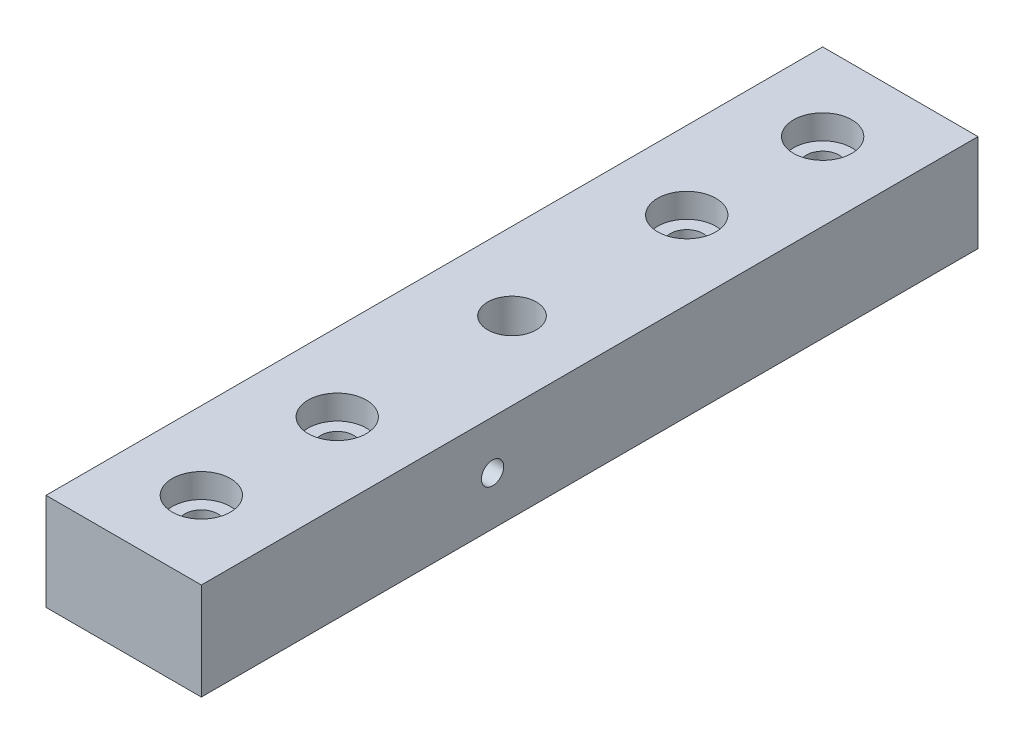
SolidWorks part; units mm, degrees
ref_plane "Ebene vorne" through (0, 0, 0) normal (0, 0, 1) x (1, 0, 0)
ref_plane "Ebene oben" through (0, 0, 0) normal (0, 1, 0) x (1, 0, 0)
ref_plane "Ebene rechts" through (0, 0, 0) normal (1, 0, 0) x (0, 0, -1)
sketch "Sketch1" plane through (0, 0, 0) normal (0, 1, 0) x (1, 0, 0)
  line L0 (0, 88.4363) -> (0, -16.8125) construction
  line L1 (-8, 80) -> (8, 80)
  line L2 (-8, 80) -> (-8, 0)
  line L3 (-8, 0) -> (8, 0)
  line L4 (8, 80) -> (8, 0)
  dimension "D1" = 16
  dimension "D2" = 80
sketch "Sketch2" plane through (0, 0, 0) normal (0, 1, 0) x (1, 0, 0)
  line L0 (0, 87.0713) -> (0, -18.1775) construction
  circle A0 centre (0, 72) radius 2.35
  circle A1 centre (0, 58) radius 2.35
  circle A2 centre (0, 22) radius 2.35
  circle A3 centre (0, 8) radius 2.35
  circle A4 centre (0, 72) radius 3
  circle A5 centre (0, 58) radius 3
  circle A6 centre (0, 22) radius 3
  circle A7 centre (0, 8) radius 3
  circle A8 centre (0, 72) radius 1.7
  circle A9 centre (0, 58) radius 1.7
  circle A10 centre (0, 22) radius 1.7
  circle A11 centre (0, 8) radius 1.7
  dimension "D3" = 4.7
  dimension "D1" = 6
  dimension "D2" = 3.4
  dimension "D4" = 14
  dimension "D5" = 14
  dimension "D6" = 50
  dimension "D7" = 8
extrude "Boss-Extrude1" add sketch "Sketch1" along normal blind 10
extrude "Cut-Extrude1" cut sketch "Sketch2" along normal blind 2.5 contours A0 | A1 | A2 | A3
extrude "Cut-Extrude2" cut sketch "Sketch2<3>" along normal through all contours A8 | A9 | A10 | A11
sketch "Sketch2<3>" plane through (0, 0, 0) normal (0, 1, 0) x (1, 0, 0) same geometry as "Sketch2"
extrude "Cut-Extrude3" cut sketch "Sketch2<4>" along normal through all from offset 7.5 contours A4 | A5 | A6 | A7
sketch "Sketch2<4>" plane through (0, 0, 0) normal (0, 1, 0) x (1, 0, 0) same geometry as "Sketch2"
sketch "Sketch3" plane through (8, 0, 0) normal (1, 0, 0) x (0, 0, -1)
  circle A0 centre (30, 5) radius 1.15
  dimension "D1" = 2.3
  dimension "D2" = 5
  dimension "D3" = 30
extrude "Cut-Extrude4" cut sketch "Sketch3" against normal through all
sketch "Sketch4" plane through (0, 10, 0) normal (0, -1, 0) x (1, 0, 0)
  line L0 (0, 0) -> (0, -80) construction
  line L1 (8, -80) -> (-8, -80) construction
  line L3 (2.2916, -44.0102) -> (4.6188, -40.0206)
  line L4 (4.6188, -40.0206) -> (2.3272, -36.0103)
  line L5 (2.3272, -36.0103) -> (-2.2916, -35.9898)
  line L6 (-2.2916, -35.9898) -> (-4.6188, -39.9794)
  line L7 (-4.6188, -39.9794) -> (-2.3272, -43.9897)
  line L8 (-2.3272, -43.9897) -> (2.2916, -44.0102)
  circle A0 centre (0, -40) radius 4 construction
  dimension "D1" = 8
extrude "Cut-Extrude5" [suppressed] cut sketch "Sketch4" along normal blind 5
sketch "Sketch6" plane through (0, 10, 0) normal (0, -1, 0) x (-1, 0, 0)
  circle A0 centre (0, 40) radius 2.5
  dimension "D1" = 5
extrude "Cut-Extrude6" cut sketch "Sketch6" along normal blind 25
